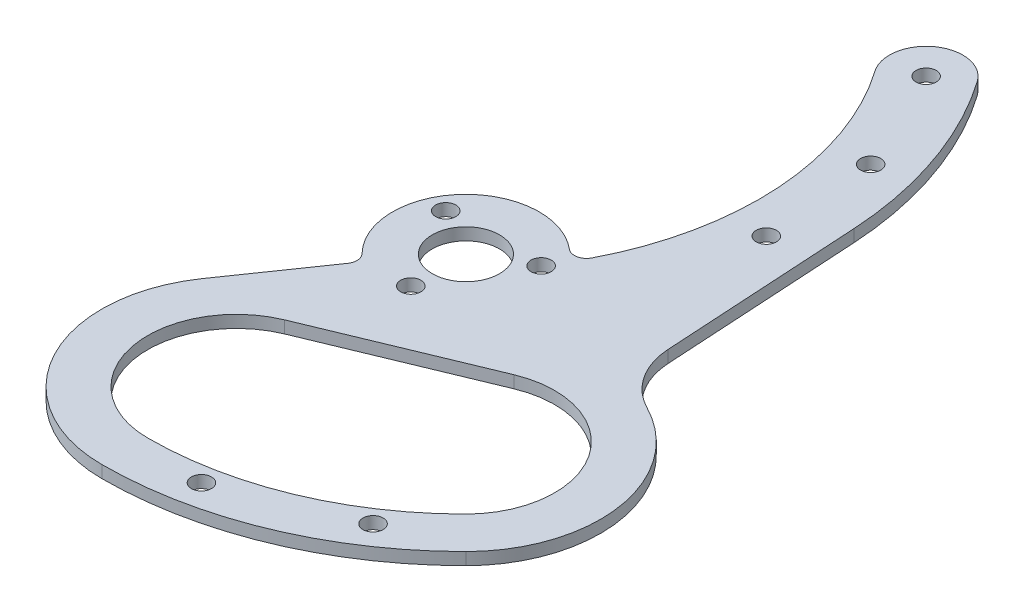
SolidWorks part; units mm, degrees
ref_plane "Спереди" through (0, 0, 0) normal (0, 0, 1) x (1, 0, 0)
ref_plane "Сверху" through (0, 0, 0) normal (0, 1, 0) x (1, 0, 0)
ref_plane "Справа" through (0, 0, 0) normal (1, 0, 0) x (0, 0, -1)
sketch "Эскиз1" plane through (0, 0, 0) normal (0, 1, 0) x (1, 0, 0)
  line L0 (0, -52) -> (0, -59.5) construction
  line L1 (36.7696, -36.7696) -> (42.0729, -42.0729) construction
  line L2 (0, -52) -> (0, 0) construction
  line L3 (0, 0) -> (0, 63.6396) construction
  line L4 (-31.8198, 31.8198) -> (0, 63.6396) construction
  line L5 (-7.3581, -9.4794) -> (-18.0878, -24.9768)
  line L6 (0, 0) -> (36.7696, -36.7696) construction
  line L7 (19.8995, -48.0417) -> (22.7697, -54.9708) construction
  line L8 (0, 0) -> (-7.7942, 4.5) construction
  line L9 (-18.0878, -24.9768) -> (30.4512, -4.8712) construction
  line L10 (0, 0) -> (7.7942, 4.5) construction
  line L11 (-31.8198, 31.8198) -> (0, 0) construction
  line L12 (-5.5489, -24.1037) -> (20.9676, -13.1203)
  line L13 (30.4512, -4.8712) -> (28.0759, 35.3565)
  line L14 (-31.8198, 31.8198) -> (0, 63.6396) construction
  line L15 (28.1802, 31.8198) -> (16.1802, 31.8198) construction
  line L18 (-31.8198, 31.8198) -> (17.3293, 66.2344) construction
  arc A0 (42.0729, -42.0729) -> (0, -59.5) centre (0, 0) cw
  arc A1 (0, -52) -> (36.7696, -36.7696) centre (0, 0) ccw
  arc A2 (0, -55) -> (21.0476, -50.8134) centre (0, 0) ccw construction
  circle A3 centre (10.73, -53.9432) radius 1.65
  circle A4 centre (30.5564, -45.7308) radius 1.65
  arc A5 (7.4995, 59.3515) -> (9.4794, 7.3581) centre (-31.8198, 31.8198) cw
  circle A6 centre (0, 0) radius 5.5
  arc A7 (17.3293, 66.2344) -> (28.0759, 35.3565) centre (-31.8198, 31.8198) cw
  arc A8 (22.1802, 31.8198) -> (12.4144, 62.7929) centre (-31.8198, 31.8198) ccw construction
  arc A9 (7.4995, 59.3515) -> (17.3293, 66.2344) centre (12.4144, 62.7929) cw
  arc A10 (9.4794, 7.3581) -> (-7.3581, -9.4794) centre (-31.8198, 31.8198) cw construction
  arc A11 (36.7696, -36.7696) -> (20.9676, -13.1203) centre (26.5165, -26.5165) ccw
  circle A13 centre (0, 0) radius 9 construction
  circle A14 centre (0, -9) radius 1.65
  circle A15 centre (-7.7942, 4.5) radius 1.65
  arc A16 (42.0729, -42.0729) -> (30.4512, -4.8712) centre (26.5165, -26.5165) ccw
  arc A18 (0, -52) -> (-5.5489, -24.1037) centre (0, -37.5) cw
  circle A19 centre (7.7942, 4.5) radius 1.65
  arc A20 (0, 0) -> (-4.1195, -3.6442) centre (-31.8198, 31.8198) ccw construction
  arc A22 (9.4794, 7.3581) -> (-7.3581, -9.4794) centre (0, 0) ccw
  arc A23 (0, -59.5) -> (-18.0878, -24.9768) centre (0, -37.5) cw
  point P1 (22.1802, 31.8198)
  point P45 (10.73, -53.9432)
  dimension "D3" = 52
  dimension "D4" = 3.3
  dimension "D7" = 90
  dimension "D8" = 120
  dimension "D9" = 11
  dimension "D10" = 90
  dimension "D11" = 18
  dimension "D12" = 48
  dimension "D14" = 60
  dimension "D20" = 22
  dimension "D16" = 29
  dimension "D17" = 12
  dimension "D18" = 10
  dimension "D5" = 55
  dimension "D6" = 45
  dimension "D15" = 120
extrude "Бобышка-Вытянуть1" add sketch "Эскиз1" along normal blind 2
sketch "Эскиз2" plane through (0, 0, 0) normal (0, -1, 0) x (1, 0, 0)
  line L0 (-31.8198, -31.8198) -> (0, 0) construction
  line L1 (-31.8198, -31.8198) -> (22.9872, -27.0248) construction
  line L2 (-31.8198, -31.8198) -> (13.7419, -63.7224) construction
  line L3 (-31.8198, -31.8198) -> (22.5978, -46.401) construction
  circle A0 centre (21.9747, -27.1134) radius 1.65
  circle A1 centre (12.4144, -62.7929) radius 1.65
  circle A2 centre (20.3402, -45.796) radius 1.65
  circle A3 centre (-31.8198, -31.8198) radius 54 construction
  point P0 (-31.8198, -31.8198)
  dimension "D3" = 3.3
  dimension "D4" = 3.3
  dimension "D5" = 3.3
  dimension "D1" = 40
  dimension "D2" = 60
  dimension "D6" = 80
extrude "Вырез-Вытянуть1" cut sketch "Эскиз2" against normal through all
fillet "Скругление1" radius 2 2 edges at (9.4794, 1, -7.3581) (-7.3581, 1, 9.4794)
fillet "Скругление2" radius 12 1 edges at (30.4512, 1, 4.8712)
